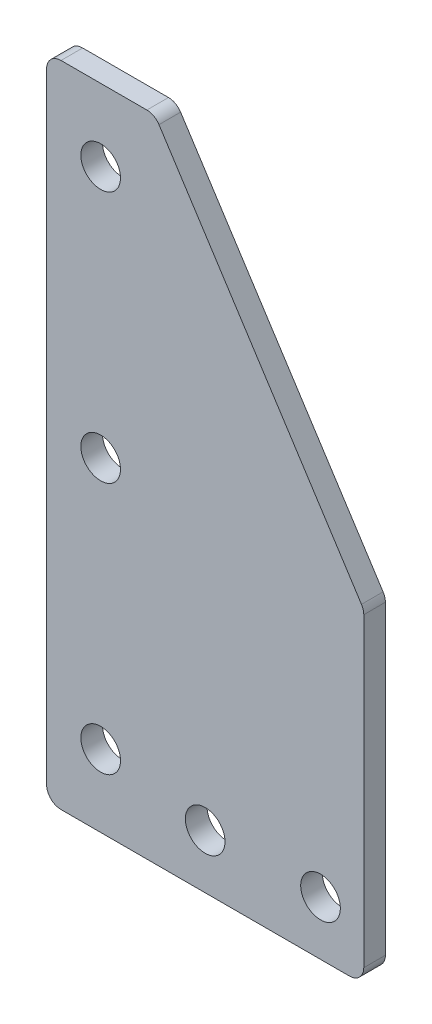
SolidWorks part; units mm, degrees
other "Objet de détail1"
ref_plane "Front" through (0, 0, 0) normal (0, 0, 1) x (1, 0, 0)
ref_plane "Top" through (0, 0, 0) normal (0, 1, 0) x (1, 0, 0)
ref_plane "Right" through (0, 0, 0) normal (1, 0, 0) x (0, 0, -1)
sketch "Esquisse1" plane through (0, 0, 0) normal (0, 0, 1) x (1, 0, 0)
  line L0 (0, 0) -> (44, 0)
  line L1 (44, 0) -> (44, 45)
  line L2 (44, 45) -> (15, 90)
  line L3 (15, 90) -> (0, 90)
  line L4 (0, 90) -> (0, 0)
  dimension "D1" = 44
  dimension "D2" = 45
  dimension "D3" = 15
  dimension "D4" = 90
extrude "Boss.-Extru.1" add sketch "Esquisse1" along normal blind 3
sketch "Esquisse2" plane through (0, 0, 3) normal (0, 0, 1) x (1, 0, 0)
  line L0 (7.5, 0) -> (7.5, 90) construction
  line L1 (0, 0) -> (44, 0) construction
  line L2 (15, 90) -> (0, 90) construction
  line L3 (44, 7.5) -> (0, 7.5) construction
  line L4 (44, 0) -> (44, 45) construction
  line L5 (0, 90) -> (0, 0) construction
  line L6 (22, 7.5) -> (22, 4.9042) construction
  line L7 (0, 45) -> (7.5, 45) construction
  circle A0 centre (7.5, 10) radius 2.75
  circle A1 centre (7.5, 45) radius 2.75
  circle A2 centre (7.5, 80) radius 2.75
  circle A4 centre (22, 7.5) radius 2.75
  circle A5 centre (38, 7.5) radius 2.75
  point P18 (0, 0)
  dimension "D1" = 5.5
  dimension "D2" = 35
  dimension "D3" = 16
  dimension "D4" = 7.5
  dimension "D6" = 6
extrude "Enlèv. mat.-Extru.1" cut sketch "Esquisse2" against normal through all both and the other way through all
fillet "Congé1" radius 2 5 edges at (44, 0, 1.5) (0, 0, 1.5) (15, 90, 1.5) (0, 90, 1.5) (44, 45, 1.5)
sketch "Esquisse3" [suppressed] plane through (0, 0, 3) normal (0, 0, 1) x (1, 0, 0)
  line L0 (38, 7.5) -> (22, 7.5) construction
  circle A0 centre (22, 7.5) radius 2.75
  circle A1 centre (38, 7.5) radius 2.75 construction
  dimension "D1" = 16
extrude "Enlèv. mat.-Extru.2" [suppressed] cut sketch "Esquisse3" against normal through all both and the other way through all
